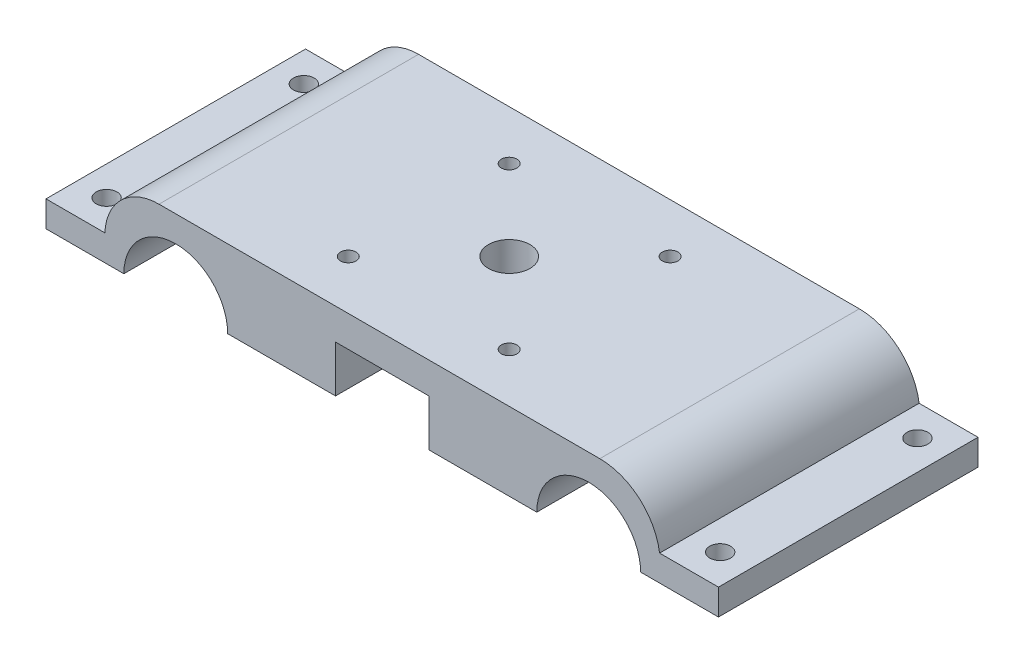
SolidWorks part; units mm, degrees
ref_plane "Piano frontale" through (0, 0, 0) normal (0, 0, 1) x (1, 0, 0)
ref_plane "Piano superiore" through (0, 0, 0) normal (0, 1, 0) x (1, 0, 0)
ref_plane "Piano destro" through (0, 0, 0) normal (1, 0, 0) x (0, 0, -1)
sketch "Schizzo1" plane through (0, 0, 0) normal (0, 0, 1) x (1, 0, 0)
  line L0 (-61.3619, 6.474) -> (38.1881, 6.474) construction
  line L1 (-61.3619, 16.474) -> (38.1881, 16.474) construction
  line L2 (-61.3619, 16.474) -> (-61.3619, -3.526) construction
  line L3 (-61.3619, -3.526) -> (38.1881, -3.526) construction
  line L4 (38.1881, 16.474) -> (38.1881, -3.526) construction
  line L5 (-11.5869, 16.474) -> (-11.5869, -3.526) construction
  line L6 (-41.3619, 6.474) -> (18.1881, 6.474)
  line L8 (38.1881, 6.474) -> (53.1881, 6.474)
  line L9 (53.1881, 6.474) -> (53.1881, 11.474)
  line L10 (53.1881, 11.474) -> (36.8484, 11.474) construction
  line L11 (-61.3619, 6.474) -> (-76.3619, 6.474)
  line L12 (-76.3619, 6.474) -> (-76.3619, 11.474)
  line L13 (-76.3619, 11.474) -> (-60.0221, 11.474) construction
  line L14 (-54.591, 21.474) -> (30.3301, 21.474)
  line L15 (-65.0221, 11.474) -> (-76.3619, 11.474)
  line L16 (53.1881, 11.474) -> (41.8484, 11.474)
  circle A0 centre (-51.3619, 6.474) radius 10 construction
  circle A1 centre (28.1881, 6.474) radius 10 construction
  arc A2 (-61.3619, 6.474) -> (-41.3619, 6.474) centre (-51.3619, 6.474) cw
  arc A3 (18.1881, 6.474) -> (38.1881, 6.474) centre (28.1881, 6.474) cw
  arc A4 (41.8484, 11.474) -> (30.3301, 21.474) centre (30.3301, 9.8405) ccw
  arc A5 (-65.0221, 11.474) -> (-54.591, 21.474) centre (-54.591, 11.0336) cw
  point P26 (-65.0221, 11.474)
  point P27 (41.8484, 11.474)
  dimension "D3" = 20
  dimension "D5" = 10
  dimension "D7" = 10
  dimension "D1" = 99.55
  dimension "D2" = 20
  dimension "D4" = 10
  dimension "D6" = 10
  dimension "D8" = 15
  dimension "D9" = 15
  dimension "D10" = 5
  dimension "D11" = 5
  dimension "D13" = 5
  dimension "D14" = 5
extrude "Estrusione-Estrusione1" add sketch "Schizzo1" along normal blind 50
sketch "Schizzo2" plane through (0, 11.474, 0) normal (0, 1, 0) x (1, 0, 0)
  line L0 (-65.0221, 0) -> (-76.3619, 0) construction
  line L1 (-76.3619, -50) -> (-76.3619, 0) construction
  line L3 (-65.0221, -50) -> (-76.3619, -50) construction
  line L4 (53.1881, -50) -> (53.1881, 0) construction
  line L5 (53.1881, -50) -> (41.8484, -50) construction
  line L6 (53.1881, 0) -> (41.8484, 0) construction
  circle A0 centre (-70.6919, -6) radius 2
  circle A1 centre (-70.6919, -44) radius 2
  circle A2 centre (47.5181, -6) radius 2
  circle A3 centre (47.5181, -44) radius 2
  dimension "D1" = 4
  dimension "D2" = 6
  dimension "D8" = 6
  dimension "D9" = 6
  dimension "D3" = 5.67
  dimension "D4" = 5.67
  dimension "D5" = 6
  dimension "D6" = 5.67
  dimension "D7" = 5.67
extrude "Taglio-Estrusione1" cut sketch "Schizzo2" against normal through all
sketch "Schizzo3" plane through (0, 0, 50) normal (0, 0, 1) x (1, 0, 0)
  line L0 (-41.3619, 6.474) -> (18.1881, 6.474) construction
  line L1 (-20.5869, 6.474) -> (-2.5869, 6.474)
  line L2 (-20.5869, 6.474) -> (-20.5869, 15.474)
  line L3 (-20.5869, 15.474) -> (-2.5869, 15.474)
  line L4 (-2.5869, 6.474) -> (-2.5869, 15.474)
  dimension "D3" = 20.775
  dimension "D1" = 9
  dimension "D2" = 18
extrude "Taglio-Estrusione2" cut sketch "Schizzo3" against normal blind 35
sketch "Schizzo4" plane through (0, 21.474, 0) normal (0, 1, 0) x (1, 0, 0)
  line L0 (-54.591, 0) -> (30.3301, -50) construction
  line L1 (30.3301, 0) -> (-54.591, -50) construction
  line L2 (3.3696, -9.5) -> (3.3696, -40.5) construction
  line L3 (3.3696, -40.5) -> (-27.6304, -40.5) construction
  line L4 (-27.6304, -40.5) -> (-27.6304, -9.5) construction
  line L5 (-27.6304, -9.5) -> (3.3696, -9.5) construction
  circle A0 centre (-12.1304, -25) radius 4
  circle A1 centre (-27.6304, -9.5) radius 1.5
  circle A2 centre (3.3696, -9.5) radius 1.5
  circle A3 centre (3.3696, -40.5) radius 1.5
  circle A4 centre (-27.6304, -40.5) radius 1.5
  dimension "D1" = 8
  dimension "D2" = 3
  dimension "D3" = 31
  dimension "D4" = 15.5
  dimension "D5" = 15.5
extrude "Taglio-Estrusione3" cut sketch "Schizzo4" against normal through all
